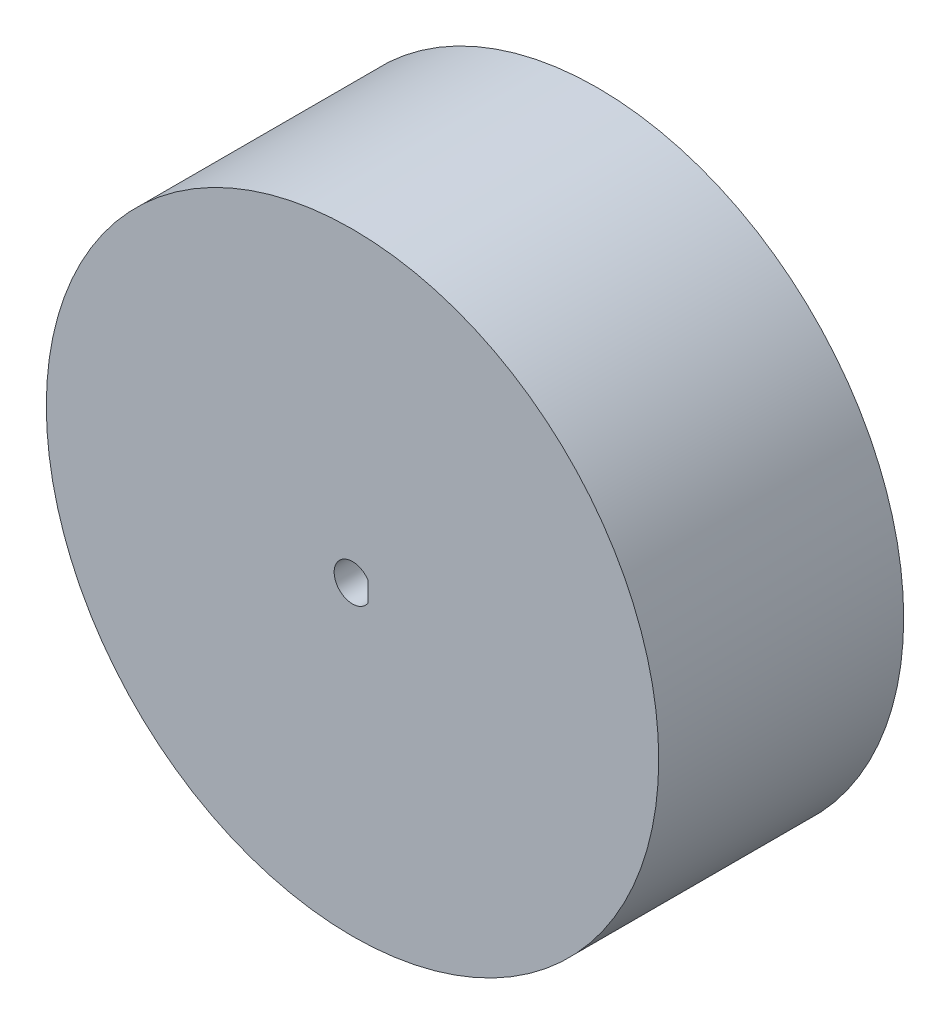
SolidWorks part; units mm, degrees
ref_plane "정면" through (0, 0, 0) normal (0, 0, 1) x (1, 0, 0)
ref_plane "윗면" through (0, 0, 0) normal (0, 1, 0) x (1, 0, 0)
ref_plane "우측면" through (0, 0, 0) normal (1, 0, 0) x (0, 0, -1)
sketch "스케치1" plane through (0, 0, 0) normal (0, 0, 1) x (1, 0, 0)
  line L0 (2.5, -5.3417) -> (2.5, -8.6583)
  circle A0 centre (0, -7) radius 50
  arc A1 (2.5, -5.3417) -> (2.5, -8.6583) centre (0, -7) ccw
  dimension "D1" = 100
extrude "보스-돌출1" add sketch "스케치1" along normal blind 40 contours A0 | A1 L0
ref_plane "평면1" through (0, 0, 20) normal (0, 0, -1) x (-1, 0, 0)
ref_axis "기준축1" through (0, -7, 40) along (0, 0, -1)
ref_point "점1"
